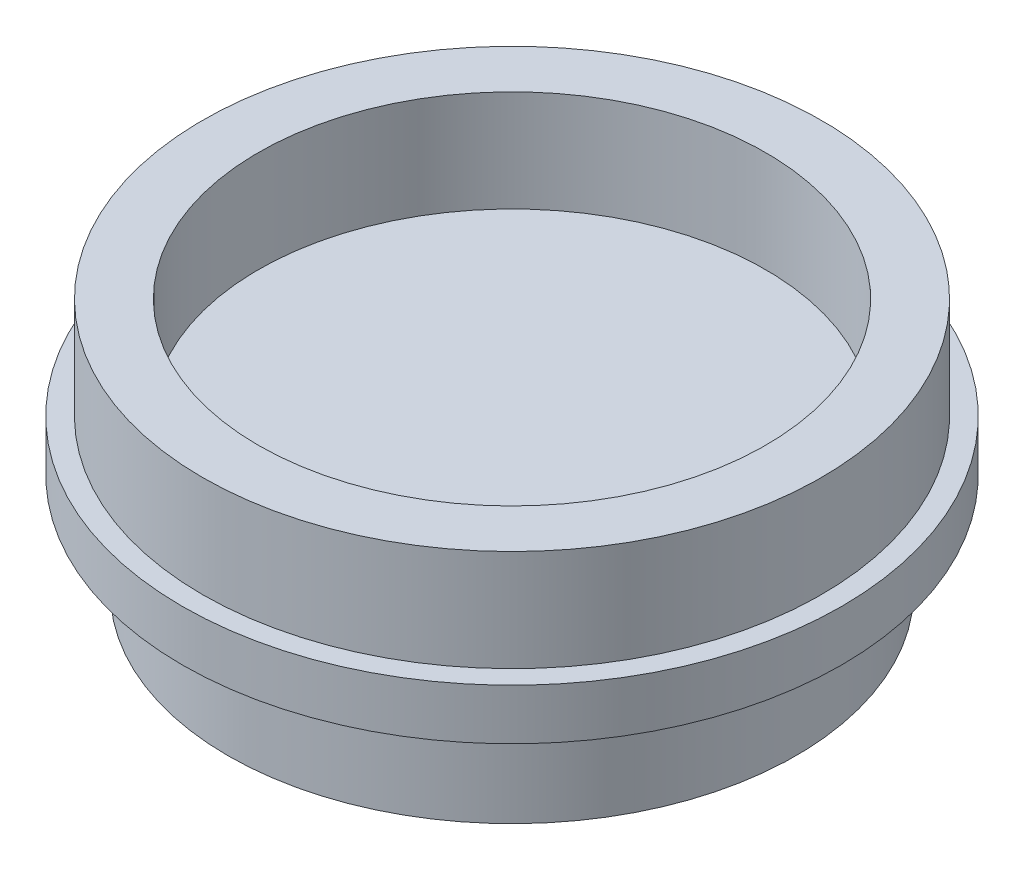
SolidWorks part; units mm, degrees
ref_plane "Front Plane" through (0, 0, 0) normal (0, 0, 1) x (1, 0, 0)
ref_plane "Top Plane" through (0, 0, 0) normal (0, 1, 0) x (1, 0, 0)
ref_plane "Right Plane" through (0, 0, 0) normal (1, 0, 0) x (0, 0, -1)
sketch "Sketch1" plane through (0, 0, 0) normal (0, 1, 0) x (1, 0, 0)
  circle A0 centre (0, 0) radius 32.5
extrude "Boss-Extrude1" add sketch "Sketch1" along normal blind 5
sketch "Sketch2" plane through (0, 0, 0) normal (0, -1, 0) x (1, 0, 0)
  circle A0 centre (0, 0) radius 22.5
  circle A1 centre (0, 0) radius 28
extrude "Boss-Extrude2" add sketch "Sketch2" along normal blind 10
sketch "Sketch3" plane through (0, 5, 0) normal (0, 1, 0) x (1, 0, 0)
  circle A0 centre (0, 0) radius 30.5
  circle A1 centre (0, 0) radius 25
extrude "Boss-Extrude3" add sketch "Sketch3" along normal blind 10
